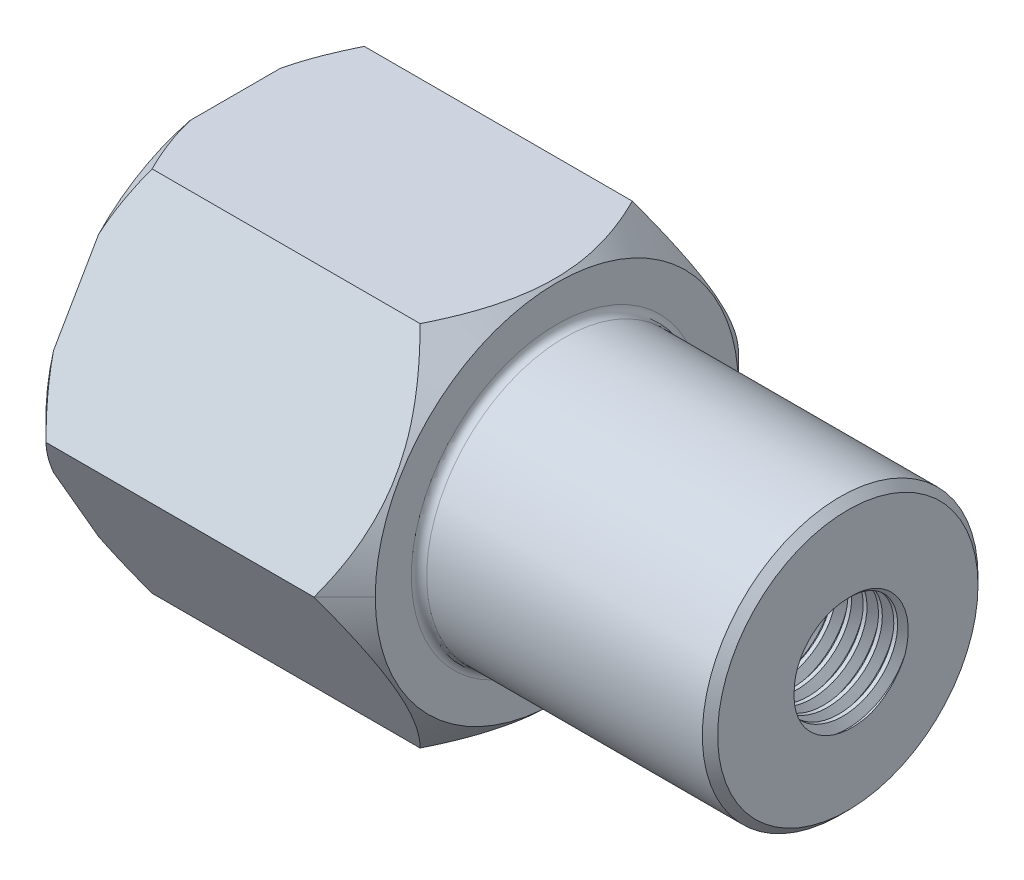
SolidWorks part; units mm, degrees
material "1.4000 (X6Cr13)"
ref_plane "Спереди" through (0, 0, 0) normal (0, 0, 1) x (1, 0, 0)
ref_plane "Сверху" through (0, 0, 0) normal (0, 1, 0) x (1, 0, 0)
ref_plane "Справа" through (0, 0, 0) normal (1, 0, 0) x (0, 0, -1)
sketch "Эскиз1" plane through (0, 0, 0) normal (1, 0, 0) x (0, 0, -1)
  line L0 (0, 0) -> (31.5086, 0) construction
  line L1 (13.8564, 0) -> (6.9282, 12)
  line L2 (6.9282, 12) -> (-6.9282, 12)
  line L3 (-6.9282, 12) -> (-13.8564, 0)
  line L4 (-13.8564, 0) -> (-6.9282, -12)
  line L5 (-6.9282, -12) -> (6.9282, -12)
  line L6 (6.9282, -12) -> (13.8564, 0)
  circle A0 centre (0, 0) radius 12 construction
  circle A1 centre (0, 0) radius 8.5
  dimension "D1" = 17
  dimension "D2" = 24
extrude "Бобышка-Вытянуть1" add sketch "Эскиз1" along normal blind 21
sketch "Эскиз2" plane through (21, 0, 0) normal (1, 0, 0) x (0, 0, -1)
  circle A0 centre (0, 0) radius 9
  circle A1 centre (0, 0) radius 4.5
  dimension "D1" = 18
  dimension "D2" = 9
extrude "Бобышка-Вытянуть2" add sketch "Эскиз2" along normal blind 10
thread "Резьба1" pitch 1 start angle 0, offset 2, length 12, pitch 1, diameter 17
ref_plane "Плоскость4" through (-2, 0, -8.5) normal (0, -1, 0) x (0, 0, -1)
sketch "Профиль резьбы1" plane through (-2, 0, -8.5) normal (0, -1, 0) x (0, 0, -1)
  line L0 (0, 0) -> (0, 1) construction
  line L1 (0, 0) -> (0.5413, 0.3125)
  line L2 (0.5413, 0.3125) -> (0.5413, 0.4375)
  line L3 (0.5413, 0.4375) -> (0, 0.75)
  line L4 (0.5413, 0.375) -> (0, 0.375) construction
  line L11 (0, 0) -> (0, 0.75)
  point P2 (0, 0)
  dimension "Pitch" = 1
  dimension "Profile_Angle" = 60
  dimension "Profile_Land" = 0.125
  dimension "Profile_Height" = 0.5413
sketch "Эскиз8" plane through (0, 0, 0) normal (0, 1, 0) x (1, 0, 0)
  line L0 (21, -13.8564) -> (19, -13.8564)
  line L1 (21, -13.8564) -> (0, -13.8564) construction
  line L2 (19, -13.8564) -> (21, -11.8564)
  line L3 (21, -11.8564) -> (21, -13.8564)
  dimension "D1" = 45
  dimension "D2" = 2
sweep "Вырез-По траектории1" cut profiles "Эскиз8" path edge at (21, 0, -9)
sketch "Эскиз9" plane through (0, 0, 0) normal (0, 1, 0) x (1, 0, 0)
  line L0 (0, 13.8564) -> (0, 12.3564)
  line L1 (0, 12.3564) -> (1.5, 13.8564)
  line L2 (19, 13.8564) -> (0, 13.8564) construction
  line L3 (1.5, 13.8564) -> (0, 13.8564)
  dimension "D1" = 45
  dimension "D2" = 1.5
sketch "Эскиз10" plane through (0, 0, 0) normal (-1, 0, 0) x (0, 0, 1)
  circle A0 centre (0, 0) radius 12
sweep "Вырез-По траектории4" cut profiles "Эскиз9" path "Эскиз10"
fillet "Скругление1" radius 0.5 1 edges at (21, 0, -9)
sketch "Эскиз11" plane through (31, 0, 0) normal (1, 0, 0) x (0, 0, -1)
  circle A0 centre (0, 0) radius 9
  circle A1 centre (0, 0) radius 3.5
  dimension "D1" = 18
  dimension "D2" = 7
extrude "Бобышка-Вытянуть3" add sketch "Эскиз11" along normal blind 9
chamfer "Фаска1" distance 0.5 angle 45 1 edges at (40, 0, -9)
thread "Резьба2" pitch 1 profile "Профиль резьбы3" start angle 0, offset 1, length 0, pitch 1, diameter 7
ref_plane "Плоскость6" through (41, 0, 3.5) normal (0, -1, 0) x (0, 0, 1)
sketch "Профиль резьбы3" plane through (41, 0, 3.5) normal (0, -1, 0) x (0, 0, 1)
  line L0 (0, 0) -> (0, 1) construction
  line L1 (0, 0) -> (0.5413, 0.3125)
  line L2 (0.5413, 0.3125) -> (0.5413, 0.4375)
  line L3 (0.5413, 0.4375) -> (0, 0.75)
  line L4 (0.5413, 0.375) -> (0, 0.375) construction
  line L11 (0, 0) -> (0, 0.75)
  point P2 (0, 0)
  dimension "Pitch" = 1
  dimension "Profile_Angle" = 60
  dimension "Profile_Land" = 0.125
  dimension "Profile_Height" = 0.5413
